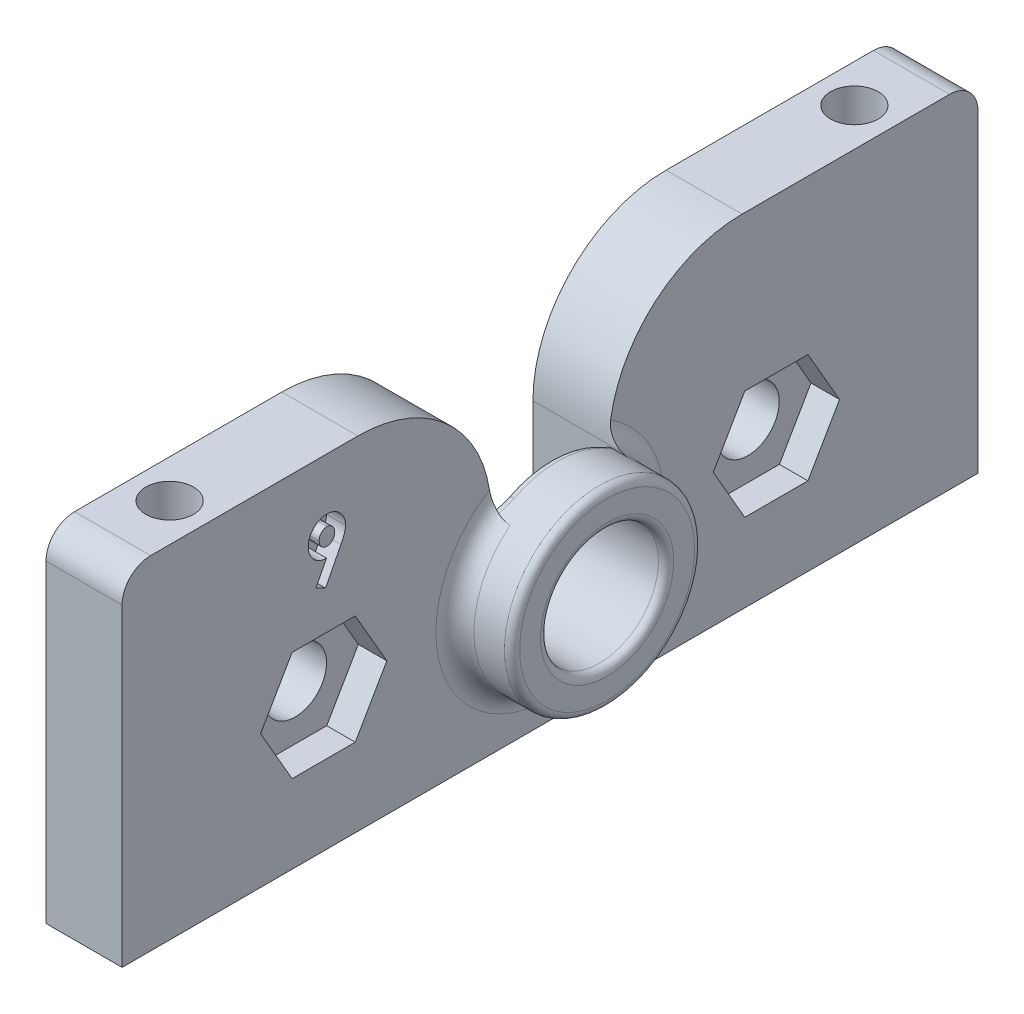
SolidWorks part; units mm, degrees
ref_plane "Front Plane" through (0, 0, 0) normal (0, 0, 1) x (1, 0, 0)
ref_plane "Top Plane" through (0, 0, 0) normal (0, 1, 0) x (1, 0, 0)
ref_plane "Right Plane" through (0, 0, 0) normal (1, 0, 0) x (0, 0, -1)
sketch "Sketch1" plane through (0, 0, 0) normal (1, 0, 0) x (0, 0, -1)
  line L1 (22.5, -9) -> (-22.5, -9)
  line L2 (22.5, -9) -> (22.5, 9)
  line L3 (22.5, 9) -> (-22.5, 9)
  line L4 (-22.5, -9) -> (-22.5, 9)
  line L5 (22.5, -9) -> (-22.5, 9) construction
  line L6 (22.5, 9) -> (-22.5, -9) construction
  point P0 (0, 0)
  dimension "D1" = 45
  dimension "D2" = 18
extrude "Boss-Extrude1" add sketch "Sketch1" along normal blind 4
sketch "Sketch2" plane through (4, 0, 0) normal (1, 0, 0) x (0, 0, -1)
  line L0 (-3.1, -2) -> (-3.1, 9)
  line L1 (22.5, 9) -> (-22.5, 9) construction
  line L2 (3.1, -2) -> (3.1, 9)
  line L3 (-22.5, -9) -> (22.5, -9) construction
  line L4 (3.1, 9) -> (-3.1, 9)
  line L6 (-9.7927, -9) -> (13.6616, -9) construction
  line L7 (-9.7927, -9) -> (-9.7927, -3.5) construction
  line L8 (-9.7927, -3.5) -> (13.6616, -3.5) construction
  line L9 (13.6616, -9) -> (13.6616, -3.5) construction
  circle A0 centre (-11.9, -2) radius 1.65
  arc A8 (-3.1, -2) -> (3.1, -2) centre (0, -2) ccw
  dimension "D3" = 3.3
  dimension "D4" = 6.2
  dimension "D5" = 11.9
  dimension "D2" = 7
  dimension "D1" = 7
  dimension "D6" = 5.5
extrude "Cut-Extrude1" cut sketch "Sketch2" against normal blind 5
mirror "Mirror1" about plane through (0, 0, 0) normal (0, 0, 1) of "Cut-Extrude1"
fillet "Fillet1" radius 1.5 2 edges at (2, 9, -22.5) (2, 9, 22.5)
sketch "Sketch6" plane through (4, 0, 0) normal (1, 0, 0) x (0, 0, -1)
  line L1 (-13.5599, -4.875) -> (-10.2401, -4.875)
  line L2 (-10.2401, -4.875) -> (-8.5802, -2)
  line L3 (-8.5802, -2) -> (-10.2401, 0.875)
  line L4 (-10.2401, 0.875) -> (-13.5599, 0.875)
  line L5 (-13.5599, 0.875) -> (-15.2198, -2)
  line L6 (-15.2198, -2) -> (-13.5599, -4.875)
  line L7 (13.5599, 0.875) -> (10.2401, 0.875)
  line L8 (10.2401, 0.875) -> (8.5802, -2)
  line L9 (8.5802, -2) -> (10.2401, -4.875)
  line L10 (10.2401, -4.875) -> (13.5599, -4.875)
  line L11 (13.5599, -4.875) -> (15.2198, -2)
  line L12 (15.2198, -2) -> (13.5599, 0.875)
  circle A1 centre (-11.9, -2) radius 2.875 construction
  circle A2 centre (11.9, -2) radius 2.875 construction
  dimension "D1" = 5.75
  dimension "D2" = 5.75
extrude "Cut-Extrude3" cut sketch "Sketch6" against normal blind 1.5
sketch "Sketch10" plane through (4, 0, 0) normal (1, 0, 0) x (0, 0, -1)
  line L0 (-3.1, 9) -> (-3.1, -2) construction
  line L1 (3.1, 9) -> (3.1, -2) construction
  arc A0 (-3.1, -2) -> (3.1, -2) centre (0, -2) ccw construction
sketch "Sketch3" plane through (4, 0, 0) normal (1, 0, 0) x (0, 0, -1)
  line L0 (-5, -2) -> (-8.5802, -2) construction
  line L3 (-3.1, -2) -> (-5, -2)
  line L4 (3.1, -2) -> (5, -2)
  line L5 (-10.2401, 0.875) -> (-8.5802, -2) construction
  line L6 (-10.0236, -4.5) -> (-4.3301, -4.5) construction
  line L7 (5, -2) -> (8.5802, -2) construction
  line L8 (-8.5802, -2) -> (-10.2401, 0.875) construction
  line L9 (10.0236, -4.5) -> (4.3301, -4.5) construction
  line L10 (8.5802, -2) -> (5, -2)
  line L11 (-22.5, 7.5) -> (-22.5, -9) construction
  line L12 (-22.5, -9) -> (22.5, -9) construction
  line L13 (-22.5, -9) -> (-22.5, -3.5) construction
  line L14 (-22.5, -3.5) -> (22.5, -3.5) construction
  line L15 (22.5, -9) -> (22.5, -3.5) construction
  line L16 (22.5, -9) -> (22.5, 7.5) construction
  line L17 (-22.5, -9) -> (22.5, -9) construction
  line L18 (-10.2401, -4.875) -> (-8.5802, -2) construction
  line L19 (10, -11.5) -> (-10, -11.5) construction
  line L20 (10, -11.5) -> (10, -3.5) construction
  line L21 (10, -3.5) -> (-10, -3.5) construction
  line L22 (-10, -11.5) -> (-10, -3.5) construction
  line L23 (10, -11.5) -> (-10, -3.5) construction
  line L24 (10, -3.5) -> (-10, -11.5) construction
  line L25 (10.2401, 0.875) -> (8.5802, -2) construction
  line L26 (10.2401, 0.875) -> (8.5802, -2) construction
  line L27 (-8.5802, -2) -> (-10.0236, -4.5) construction
  line L28 (8.5802, -2) -> (10.2401, -4.875) construction
  line L29 (8.5802, -2) -> (10.0236, -4.5) construction
  arc A1 (-5, -2) -> (5, -2) centre (0, -2) ccw
  arc A2 (-3.1, -2) -> (3.1, -2) centre (0, -2) ccw construction
  arc A3 (-3.1, -2) -> (3.1, -2) centre (0, -2) ccw
  arc A4 (-3.1, -2) -> (3.1, -2) centre (0, -2) ccw construction
  point P24 (0, -7.5)
  arc M6 (3.1, -2) -> (-3.1, -2) centre (0, -2) cw
  dimension "D1" = 5.5
  dimension "D2" = 8
  dimension "D3" = 5
  dimension "D4" = 2.5
  dimension "D8" = 20
extrude "Boss-Extrude4" [suppressed] add sketch "Sketch3" along normal blind 5 contours L3 A1 L4 M6
sketch "Sketch16" plane through (4, 0, 0) normal (1, 0, 0) x (0, 0, -1)
  circle A0 centre (0, -2) radius 3.1
  circle A1 centre (0, -2) radius 5
  arc A3 (-3.1, -2) -> (3.1, -2) centre (0, -2) ccw construction
  arc A4 (-5, -2) -> (5, -2) centre (0, -2) ccw construction
extrude "Boss-Extrude5" add sketch "Sketch16" along normal blind 3
sketch "Sketch11" [suppressed] plane through (0, 0, 0) normal (-1, 0, 0) x (0, 0, 1)
  line L0 (4, -2) -> (-4, -2) construction
  line L2 (-4, -2) -> (-4, 10.093)
  line L4 (-4, 10.093) -> (4, 10.093)
  line L5 (4, 10.093) -> (4, -2)
  circle A0 centre (0, -2) radius 4 construction
  arc A1 (4, -2) -> (-4, -2) centre (0, -2) cw
  dimension "D1" = 8
extrude "Cut-Extrude6" [suppressed] cut sketch "Sketch11" against normal up to surface (4 mm away)
sketch "Sketch4" plane through (0, -9, 0) normal (0, -1, 0) x (1, 0, 0)
  line L0 (2, 22.5) -> (2, -22.5) construction
  line L1 (4, 22.5) -> (0, 22.5) construction
  line L2 (4, -22.5) -> (0, -22.5) construction
  circle A0 centre (2, 18) radius 1.25
  circle A1 centre (2, -18) radius 1.25
  dimension "D1" = 2.5
  dimension "D2" = 2.5
  dimension "D3" = 18
  dimension "D4" = 18
extrude "Cut-Extrude2" cut sketch "Sketch4" against normal up to surface (18 mm away) up to face at (2, 9, 12.05)
fillet "Fillet9" radius 7 2 edges at (2, 9, 3.1) (2, 9, -3.1)
sketch "Sketch13" plane through (4, 0, 0) normal (1, 0, 0) x (0, 0, -1)
  text T0 "<b>9</b>"
extrude "Cut-Extrude7" cut sketch "Sketch13" against normal blind 1
fillet "Fillet18" radius 1 2 edges at (4, -0.0385, -3.1) (4, -0.0385, 3.1)
fillet "Fillet17" radius 1 1 edges at (4, -7, 0)
fillet "Fillet19" radius 0.4 5 edges at (7, -2, -5) (7, -2, -3.1) (3.5341, 2.0403, -2.9454) (3.734, 2.1565, 2.7792) (4, 3, 0)
